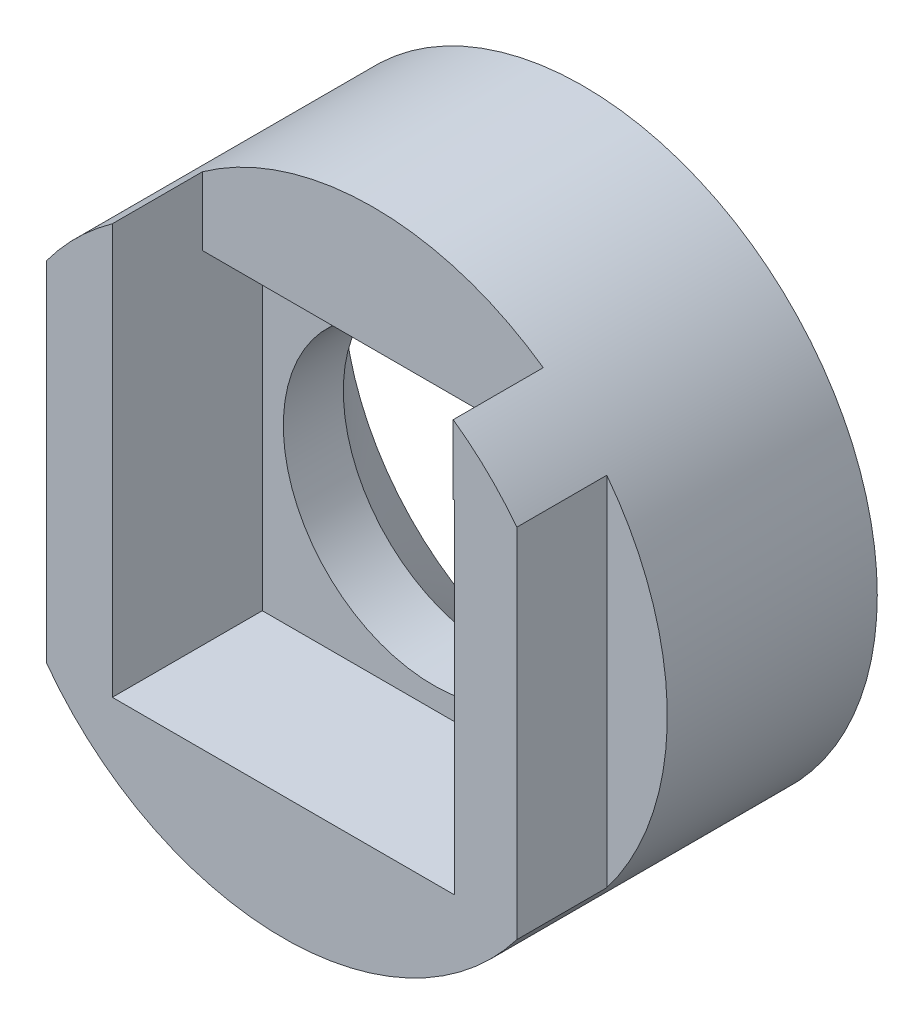
SolidWorks part; units mm, degrees
ref_plane "Front Plane" through (0, 0, 0) normal (0, 0, 1) x (1, 0, 0)
ref_plane "Top Plane" through (0, 0, 0) normal (0, 1, 0) x (1, 0, 0)
ref_plane "Right Plane" through (0, 0, 0) normal (1, 0, 0) x (0, 0, -1)
sketch "Sketch1" plane through (0, 0, 0) normal (0, 0, 1) x (1, 0, 0)
  circle A0 centre (0, 0) radius 9.8
  circle A1 centre (0, 0) radius 5
  dimension "D1" = 19.6
  dimension "D2" = 10
extrude "Boss-Extrude1" add sketch "Sketch1" along normal blind 10
sketch "Sketch2" plane through (0, 0, 10) normal (0, 0, 1) x (1, 0, 0)
  line L1 (-5.7, 5.7) -> (5.7, 5.7)
  line L2 (-5.7, 5.7) -> (-5.7, -5.7)
  line L3 (-5.7, -5.7) -> (5.7, -5.7)
  line L4 (5.7, 5.7) -> (5.7, -5.7)
  point P4 (5.7, 0)
  point P5 (0, 5.7)
  dimension "D1" = 11.4
  dimension "D2" = 11.4
extrude "Cut-Extrude1" cut sketch "Sketch2" against normal blind 5
sketch "Sketch3" plane through (0, 0, 10) normal (0, 0, 1) x (1, 0, 0)
  line L1 (-5.7, 5.7) -> (5.6634, 5.7)
  line L2 (-5.7, 5.7) -> (-5.7, 10.3571)
  line L3 (-5.7, 10.3571) -> (5.6634, 10.3571)
  line L4 (5.6634, 5.7) -> (5.6634, 10.3571)
extrude "Cut-Extrude2" cut sketch "Sketch3" against normal blind 3
sketch "Sketch4" plane through (0, 0, 10) normal (0, 0, 1) x (1, 0, 0)
  line L1 (-13.2922, 9.0382) -> (-7.8874, 9.0382)
  line L2 (-13.2922, 9.0382) -> (-13.2922, -9.0382)
  line L3 (-13.2922, -9.0382) -> (-7.8874, -9.0382)
  line L4 (-7.8874, 9.0382) -> (-7.8874, -9.0382)
  line L5 (13.4474, 9.0382) -> (7.784, 9.0382)
  line L6 (13.4474, 9.0382) -> (13.4474, -8.9089)
  line L7 (13.4474, -8.9089) -> (7.784, -8.9089)
  line L8 (7.784, 9.0382) -> (7.784, -8.9089)
  point P8 (-7.8874, -9.0382)
extrude "Cut-Extrude3" cut sketch "Sketch4" against normal blind 3
chamfer "Chamfer1" distance 3 angle 45 1 edges at (5, 0, 0)
